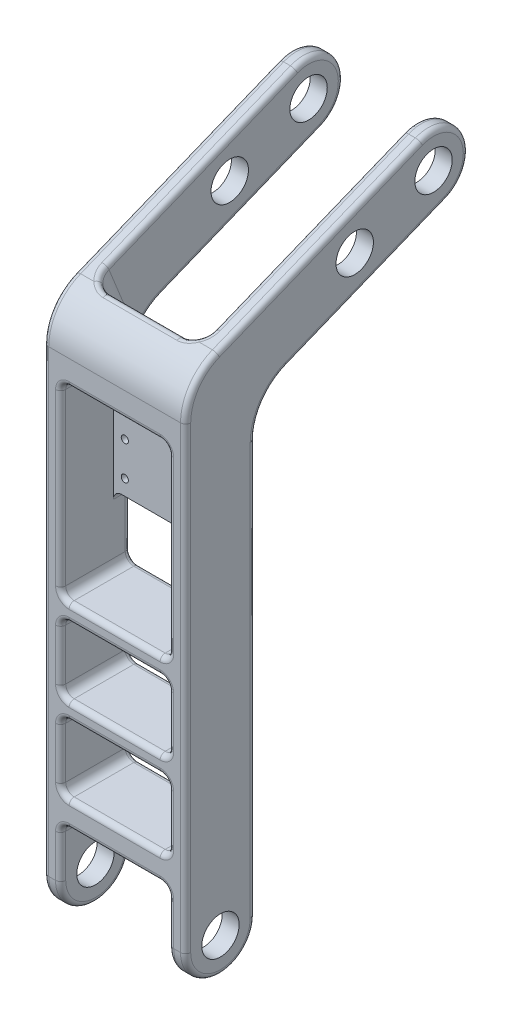
SolidWorks part; units mm, degrees
ref_plane "前视基准面" through (0, 0, 0) normal (0, 0, 1) x (1, 0, 0)
ref_plane "上视基准面" through (0, 0, 0) normal (0, 1, 0) x (1, 0, 0)
ref_plane "右视基准面" through (0, 0, 0) normal (1, 0, 0) x (0, 0, -1)
sketch "草图1" plane through (0, 0, 0) normal (0, 0, 1) x (1, 0, 0)
  line L0 (0, 0) -> (0, 40)
  line L1 (0, 40) -> (83.5, 40)
  line L2 (83.5, 40) -> (83.5, 0)
  line L3 (83.5, 0) -> (73.5, 0)
  line L4 (73.5, 0) -> (73.5, 30)
  line L5 (73.5, 30) -> (10, 30)
  line L6 (10, 30) -> (10, 0)
  line L7 (10, 0) -> (0, 0)
  dimension "D1" = 63.5
  dimension "D2" = 10
  dimension "D3" = 30
  dimension "D4" = 10
extrude "凸台-拉伸1" add sketch "草图1" along normal blind 41
sketch "草图2" plane through (83.5, 0, 0) normal (1, 0, 0) x (0, 0, -1)
  line L0 (-41, 0) -> (0, 0)
  arc A0 (-41, 0) -> (0, 0) centre (-20.5, 0) ccw
extrude "凸台-拉伸2" add sketch "草图2" against normal blind 10
sketch "草图3" plane through (83.5, 0, 0) normal (1, 0, 0) x (0, 0, -1)
  circle A0 centre (-20.5, 0) radius 11
  dimension "D1" = 22
extrude "切除-拉伸1" cut sketch "草图3" against normal blind 10
ref_plane "基准面4" through (41.75, 0, 0) normal (1, 0, 0) x (0, 0, -1)
mirror "镜向1" about plane through (41.75, 0, 0) normal (1, 0, 0) of "凸台-拉伸2", "切除-拉伸1"
sketch "草图4" plane through (0, 40, 0) normal (0, 1, 0) x (1, 0, 0)
  line L0 (83.5, 0) -> (0, 0) construction
  line L1 (0, 0) -> (83.5, 0)
  line L2 (0, 0) -> (0, -41)
  line L3 (0, -41) -> (83.5, -41)
  line L4 (83.5, 0) -> (83.5, -41)
  line L5 (83.5, -41) -> (0, -41) construction
  line L6 (41.75, -41) -> (41.75, 5.4834) construction
extrude "凸台-拉伸3" add sketch "草图4" along normal blind 250
sketch "草图5" plane through (0, 0, 41) normal (0, 0, 1) x (1, 0, 0)
  line L0 (83.5, 0) -> (83.5, 290) construction
  line L1 (15, 45) -> (68.5, 45)
  line L2 (10, 50) -> (10, 80)
  line L3 (15, 85) -> (68.5, 85)
  line L4 (73.5, 50) -> (73.5, 80)
  line L5 (0, 290) -> (0, 0) construction
  line L6 (10, 30) -> (73.5, 30) construction
  line L23 (10, 100) -> (10, 130)
  line L24 (15, 95) -> (68.5, 95)
  line L25 (73.5, 100) -> (73.5, 130)
  line L26 (15, 135) -> (68.5, 135)
  line L27 (10, 150) -> (10, 180)
  line L28 (15, 145) -> (68.5, 145)
  line L29 (73.5, 150) -> (73.5, 180)
  line L30 (15, 185) -> (68.5, 185)
  arc A0 (68.5, 45) -> (73.5, 50) centre (68.5, 50) ccw
  arc A1 (68.5, 85) -> (73.5, 80) centre (68.5, 80) cw
  arc A2 (15, 45) -> (10, 50) centre (15, 50) cw
  arc A3 (10, 80) -> (15, 85) centre (15, 80) cw
  arc A20 (10, 130) -> (15, 135) centre (15, 130) cw
  arc A21 (15, 95) -> (10, 100) centre (15, 100) cw
  arc A22 (68.5, 95) -> (73.5, 100) centre (68.5, 100) ccw
  arc A23 (68.5, 135) -> (73.5, 130) centre (68.5, 130) cw
  arc A24 (10, 180) -> (15, 185) centre (15, 180) cw
  arc A25 (15, 145) -> (10, 150) centre (15, 150) cw
  arc A26 (68.5, 145) -> (73.5, 150) centre (68.5, 150) ccw
  arc A27 (68.5, 185) -> (73.5, 180) centre (68.5, 180) cw
  point P10 (73.5, 45)
  point P13 (73.5, 85)
  dimension "D4" = 5
  dimension "D1" = 10
  dimension "D2" = 10
  dimension "D3" = 40
  dimension "D5" = 15
  dimension "D6" = 3
extrude "切除-拉伸2" cut sketch "草图5" against normal blind 309
sketch "草图7" plane through (83.5, 0, 0) normal (1, 0, 0) x (0, 0, -1)
  line L0 (0, 262.3452) -> (112.4864, 307.7926)
  line L1 (112.4864, 307.7926) -> (97.1275, 345.8071)
  line L2 (97.1275, 345.8071) -> (-41, 290)
  line L3 (-41, 290) -> (0, 262.3452)
  line L4 (0, 0) -> (0, 290) construction
  circle A1 centre (-20.5, 0) radius 11 construction
  point P3 (104.807, 326.7999)
  dimension "D1" = 350
  dimension "D2" = 112
  dimension "D3" = 41
extrude "凸台-拉伸5" add sketch "草图7" against normal up to surface (83.5 mm away) up to face at (0, 11, 20.5)
sketch "草图8" plane through (41.75, 0, 0) normal (1, 0, 0) x (0, 0, -1)
  line L0 (0, 232.3452) -> (0, 192.3452)
  line L1 (55, 192.3452) -> (55, 210.3452)
  line L2 (0, 192.3452) -> (55, 192.3452)
  line L5 (55, 210.3452) -> (0, 232.3452)
  line L7 (0, 0) -> (0, 262.3452) construction
  dimension "D1" = 70
  dimension "D2" = 55
  dimension "D3" = 40
  dimension "D4" = 18
extrude "凸台-拉伸6" add sketch "草图8" along normal mid plane 83.5
fillet "圆角1" radius 8 1 edges at (41.75, 192.3452, -55)
sketch "草图10" plane through (83.5, 0, 0) normal (1, 0, 0) x (0, 0, -1)
  circle A0 centre (47, 200.3452) radius 5.5
  dimension "D1" = 11
extrude "切除-拉伸3" cut sketch "草图10" against normal blind 92
sketch "草图11" [suppressed] plane through (52.25, 0, 0) normal (1, 0, 0) x (0, 0, -1)
  line L0 (55, 283.0172) -> (15, 241.915)
  line L1 (55, 242.0172) -> (55, 298.0172) construction
  line L2 (15, 241.915) -> (15, 227.0172)
  line L3 (0, 227.0172) -> (40, 227.0172) construction
  line L4 (15, 227.0172) -> (64.4389, 227.0172)
  line L5 (64.4389, 227.0172) -> (55, 283.0172)
  line L6 (0, 0) -> (0, 243.0172) construction
  dimension "D1" = 15
  dimension "D2" = 15
fillet "圆角2" [suppressed] radius 5
sketch "草图13" plane through (41.75, 0, 0) normal (1, 0, 0) x (0, 0, -1)
  circle A0 centre (47, 200.3452) radius 6
  circle A1 centre (47, 200.3452) radius 5
  dimension "D1" = 10
extrude "凸台-拉伸8" [suppressed] add sketch "草图13" along normal mid plane 1
sketch "草图14" plane through (41.75, 0, 0) normal (1, 0, 0) x (0, 0, -1)
  line L0 (97.1275, 345.8071) -> (112.4864, 307.7926)
  arc A0 (97.1275, 345.8071) -> (112.4864, 307.7926) centre (104.807, 326.7999) cw
extrude "凸台-拉伸9" add sketch "草图14" against normal mid plane 83.5
sketch "草图15" plane through (83.5, 0, 0) normal (1, 0, 0) x (0, 0, -1)
  line L0 (0, 262.3452) -> (112.4864, 307.7926) construction
  circle A0 centre (104.807, 326.7999) radius 11
  circle A1 centre (58.4478, 308.0696) radius 11
  dimension "D1" = 22
  dimension "D2" = 22
  dimension "D3" = 50
  dimension "D4" = 20.5
extrude "切除-拉伸5" cut sketch "草图15" against normal mid plane 185
sketch "草图16" plane through (0, 263.5448, 106.479) normal (0, 0.9272, 0.3746) x (1, 0, 0)
  line L0 (83.5, 240.0967) -> (0, 240.0967) construction
  line L1 (10, 240.0967) -> (73.5, 240.0967)
  line L2 (10, 240.0967) -> (10, 90.0967)
  line L3 (10, 90.0967) -> (73.5, 90.0967)
  line L4 (73.5, 240.0967) -> (73.5, 90.0967)
  line L5 (83.5, 219.5967) -> (83.5, 70.6214) construction
  line L6 (0, 70.6214) -> (0, 219.5967) construction
  dimension "D1" = 10
  dimension "D2" = 10
  dimension "D3" = 150
extrude "切除-拉伸6" cut sketch "草图16" against normal blind 65
sketch "草图17" plane through (10, 0, 0) normal (1, 0, 0) x (0, 0, -1)
  circle A0 centre (58.4478, 308.0696) radius 9.5
  circle A1 centre (58.4478, 308.0696) radius 7.5
  dimension "D1" = 15
extrude "凸台-拉伸10" [suppressed] add sketch "草图17" against normal blind 4
sketch "草图18" [suppressed] plane through (73.5, 0, 0) normal (-1, 0, 0) x (0, 0, 1)
  circle A0 centre (-35.6394, 310.5764) radius 7.5
  circle A1 centre (-35.6394, 310.5764) radius 9.5
extrude "凸台-拉伸11" [suppressed] add sketch "草图18" against normal blind 4
fillet "圆角3" radius 30 3 edges at (41.75, 290, 41) (78.5, 262.3452, 0) (5, 262.3452, 0)
extrude "切除-拉伸7" cut sketch "草图8<2>" against normal mid plane 75.5
sketch "草图8<2>" plane through (41.75, 0, 0) normal (1, 0, 0) x (0, 0, -1) same geometry as "草图8"
fillet "圆角4" [suppressed] radius 8
sketch "草图19" plane through (83.5, 0, 0) normal (1, 0, 0) x (0, 0, -1)
  line L1 (0, 232.3452) -> (70.1752, 232.3452)
  line L2 (0, 232.3452) -> (0, 190.676)
  line L3 (0, 190.676) -> (70.1752, 190.676)
  line L4 (70.1752, 232.3452) -> (70.1752, 190.676)
extrude "切除-拉伸8" cut sketch "草图19" against normal blind 90.5
sketch "草图20" plane through (0, 0, 0) normal (0, 0, -1) x (-1, 0, 0)
  line L1 (-66.75, 214) -> (-16.75, 214) construction
  line L2 (-66.75, 214) -> (-66.75, 194) construction
  line L3 (-66.75, 194) -> (-16.75, 194) construction
  line L4 (-16.75, 214) -> (-16.75, 194) construction
  line L5 (-66.75, 214) -> (-16.75, 194) construction
  line L6 (-66.75, 194) -> (-16.75, 214) construction
  point P0 (-41.75, 204)
  dimension "D1" = 41.75
  dimension "D2" = 204
  dimension "D3" = 20
  dimension "D4" = 50
hole_wizard "M5 螺纹孔的螺纹孔钻头1" positions "3D草图1" profile "草图21" hole size "M5" standard "GB"
sketch3d "3D草图1"
  point P0 (66.75, 214, 0)
  point P3 (16.75, 214, 0)
  point P6 (16.75, 194, 0)
  point P9 (66.75, 194, 0)
sketch "草图21" plane through (66.75, 214, 0) normal (1, 0, 0) x (0, 1, 0)
  line L0 (0, 0) -> (0, 11.2618)
  line L1 (0, 11.2618) -> (2.1, 10)
  line L2 (2.1, 10) -> (2.1, 0)
  line L5 (2.1, 0) -> (0, 0)
  line L10 (0, 11.2618) -> (-2.1, 10) construction
  line L11 (0, -6.35) -> (0, 107.95) construction
  dimension "孔直径" = 4.2
  dimension "孔深度" = 10
  dimension "导头角度" = 118
fillet "圆角5" radius 10 2 edges at (10, 268.8985, 11.4696) (73.5, 268.8985, 11.4696)
sketch "草图22" plane through (0, 0, 41) normal (0, 0, 1) x (1, 0, 0)
  line L2 (10, 190) -> (10, 250)
  line L3 (15, 255) -> (68.5, 255)
  line L4 (73.5, 190) -> (73.5, 250)
  line L5 (10, 190) -> (10, 180)
  line L6 (10, 180) -> (10, 150) construction
  line L7 (73.5, 150) -> (73.5, 180) construction
  line L8 (10, 180) -> (73.5, 180)
  line L9 (73.5, 180) -> (73.5, 190)
  arc A0 (10, 250) -> (15, 255) centre (15, 250) cw
  arc A1 (68.5, 255) -> (73.5, 250) centre (68.5, 250) cw
  point P0 (74.3807, 181.0431)
  point P10 (73.5, 255)
  point P13 (73.5, 180)
  dimension "D3" = 5
  dimension "D2" = 75
extrude "切除-拉伸9" cut sketch "草图22" against normal blind 31
fillet "圆角7" radius 5 2 edges at (73.5, 30, 20.5) (10, 30, 20.5)
fillet "圆角6" radius 3 94 edges at (73.5, 12.5, 0) (73.5, -20.5, 20.5) (10, 12.5, 0) (10, -20.5, 20.5) (0, 286.5405, 35.8711) (0, 321.6937, -37.4447) (0, 334.4793, -123.8142) (0, 288.859, -65.6241) (0, 258.8857, -5.1289) (0, 121.0549, 0) (0, -20.5, 20.5) (83.5, -20.5, 20.5) (83.5, 121.0549, 0) (83.5, 258.8857, -5.1289) (83.5, 288.859, -65.6241) (83.5, 334.4793, -123.8142) (83.5, 321.6937, -37.4447) (83.5, 286.5405, 35.8711) (65.2309, 240.9132, 0) (69.9587, 246.1488, -0.2731) (73.5, 264.7741, -10.3446) (73.5, 288.859, -65.6241) (73.5, 334.4793, -123.8142) (73.5, 323.4244, -41.7283) (71.8138, 298.9599, 18.8234) (41.75, 297.2867, 22.9392) (11.6862, 298.9599, 18.8234) (10, 323.4244, -41.7283) (10, 334.4793, -123.8142) (10, 288.859, -65.6241) (10, 264.7741, -10.3446) (10.7056, 252.6354, -1.9071) (18.2691, 240.9132, 0) (11.4645, 183.5355, 0) (10, 165, 0) (11.4645, 146.4645, 0) (41.75, 145, 0) (72.0355, 146.4645, 0) (73.5, 165, 0) (72.0355, 183.5355, 0) (72.0355, 46.4645, 0) (73.5, 65, 0) (72.0355, 83.5355, 0) (41.75, 85, 0) (11.4645, 83.5355, 0) (10, 65, 0) (11.4645, 46.4645, 0) (72.0355, 96.4645, 0) (73.5, 115, 0) (72.0355, 133.5355, 0) (41.75, 135, 0) (11.4645, 133.5355, 0) (10, 115, 0) (11.4645, 96.4645, 0) (73.5, 12.5, 41) (41.75, 30, 41) (10, 12.5, 41) (0, 134.8824, 41) (83.5, 134.8824, 41) (41.75, 255, 41) (11.4645, 253.5355, 41) (10, 200, 41) (11.4645, 146.4645, 41) (41.75, 145, 41) (72.0355, 146.4645, 41) (73.5, 200, 41) (72.0355, 253.5355, 41) (72.0355, 133.5355, 41) (41.75, 135, 41) (11.4645, 133.5355, 41) (10, 115, 41) (11.4645, 96.4645, 41) (41.75, 95, 41) (72.0355, 96.4645, 41) (73.5, 115, 41) (72.0355, 83.5355, 41) (41.75, 85, 41) (11.4645, 83.5355, 41) (10, 65, 41) (11.4645, 46.4645, 41) (41.75, 45, 41) (72.0355, 46.4645, 41) (73.5, 65, 41) (41.75, 30, 0) (41.75, 240.5103, 0) (41.75, 185, 0) (41.75, 45, 0) (41.75, 95, 0) (11.4645, 28.5355, 0) (72.0355, 28.5355, 0) (72.0355, 28.5355, 41) (11.4645, 28.5355, 41)
sketch "草图23" plane through (83.5, 0, 0) normal (1, 0, 0) x (0, 0, -1)
  line L0 (-20.5, 0) -> (104.807, 326.7999) construction
  line L1 (104.807, 326.7999) -> (-20.5, 276.1726) construction
  line L2 (-20.5, 276.1726) -> (-20.5, 0) construction
  line L3 (97.1275, 345.8071) -> (-22.2382, 297.5803) construction
  dimension "D1" = 112
  dimension "D2" = 20.979
ref_plane "基准面5" through (0, 6.8529, 17.8723) normal (0, -0.358, -0.9337) x (0, 0.9337, -0.358)
